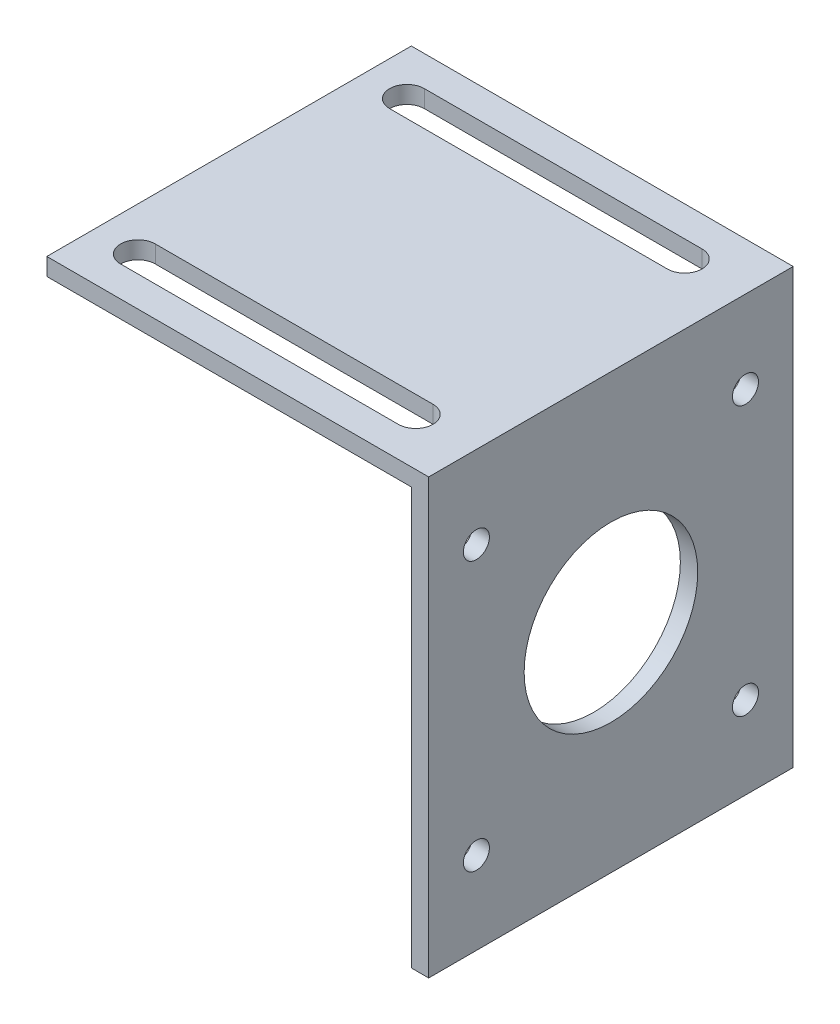
SolidWorks part; units mm, degrees
ref_plane "前视基准面" through (0, 0, 0) normal (0, 0, 1) x (1, 0, 0)
ref_plane "上视基准面" through (0, 0, 0) normal (0, 1, 0) x (1, 0, 0)
ref_plane "右视基准面" through (0, 0, 0) normal (1, 0, 0) x (0, 0, -1)
sketch "草图2" plane through (0, 0, 0) normal (1, 0, 0) x (0, 0, -1)
  line L0 (23.1, 0) -> (-23.1, 0) construction
  line L1 (-21, -25) -> (21, -25)
  line L2 (-21, -25) -> (-21, 25)
  line L3 (-21, 25) -> (21, 25)
  line L4 (21, -25) -> (21, 25)
  line L5 (-21, -25) -> (21, 25) construction
  line L6 (-21, 25) -> (21, -25) construction
  line L7 (-15.5, -15.5) -> (15.5, -15.5) construction
  line L8 (-15.5, -15.5) -> (-15.5, 15.5) construction
  line L9 (-15.5, 15.5) -> (15.5, 15.5) construction
  line L10 (15.5, -15.5) -> (15.5, 15.5) construction
  line L11 (-15.5, -15.5) -> (15.5, 15.5) construction
  line L12 (-15.5, 15.5) -> (15.5, -15.5) construction
  line L13 (0, 23.1) -> (0, -23.1) construction
  circle A0 centre (15.5, 15.5) radius 1.5
  circle A1 centre (15.5, -15.5) radius 1.5
  circle A2 centre (-15.5, -15.5) radius 1.5
  circle A3 centre (-15.5, 15.5) radius 1.5
  circle A4 centre (0, 0) radius 10
  point P0 (0, 0)
  point P6 (0, 0)
  dimension "D5" = 3
  dimension "D6" = 20
  dimension "D1" = 42
  dimension "D2" = 50
  dimension "D3" = 31
  dimension "D4" = 31
extrude "凸台-拉伸5" add sketch "草图2" along normal blind 2
sketch "草图4" plane through (0, 0, 0) normal (0, 1, 0) x (1, 0, 0)
  line L0 (-37, 15.5) -> (-5, 15.5) construction
  line L1 (-42, -21) -> (0, -21)
  line L2 (-42, -21) -> (-42, 21)
  line L3 (-42, 21) -> (0, 21)
  line L4 (0, -21) -> (0, 21)
  line L5 (-42, -21) -> (0, 21) construction
  line L6 (-42, 21) -> (0, -21) construction
  line L7 (-37, 17.5) -> (-5, 17.5)
  line L8 (-37, 13.5) -> (-5, 13.5)
  line L9 (-1.1, 0) -> (1.1, 0) construction
  line L10 (-37, -15.5) -> (-5, -15.5) construction
  line L11 (-37, -17.5) -> (-5, -17.5)
  line L12 (-37, -13.5) -> (-5, -13.5)
  arc A0 (-37, 17.5) -> (-37, 13.5) centre (-37, 15.5) ccw
  arc A1 (-5, 13.5) -> (-5, 17.5) centre (-5, 15.5) ccw
  arc A2 (-37, -17.5) -> (-37, -13.5) centre (-37, -15.5) cw
  arc A3 (-5, -13.5) -> (-5, -17.5) centre (-5, -15.5) cw
  point P0 (-21, 0)
  point P9 (-21, 15.5)
  point P18 (-21, -15.5)
  dimension "D6" = 2
  dimension "D1" = 21
  dimension "D2" = 42
  dimension "D3" = 42
  dimension "D4" = 15.5
  dimension "D5" = 32
extrude "凸台-拉伸6" add sketch "草图4" along normal blind 25
extrude "切除-拉伸1" cut sketch "草图4<3>" along normal blind 23
sketch "草图4<3>" plane through (0, 0, 0) normal (0, 1, 0) x (1, 0, 0) same geometry as "草图4"
